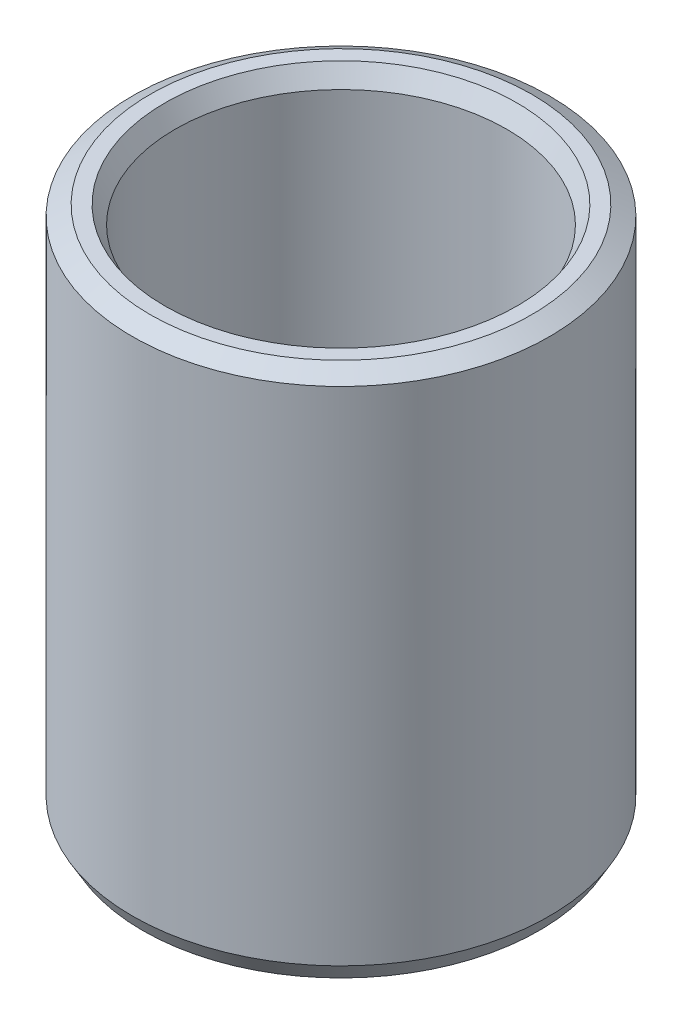
SolidWorks part; units mm, degrees
ref_plane "Front Plane" through (0, 0, 0) normal (0, 0, 1) x (1, 0, 0)
ref_plane "Top Plane" through (0, 0, 0) normal (0, 1, 0) x (1, 0, 0)
ref_plane "Right Plane" through (0, 0, 0) normal (1, 0, 0) x (0, 0, -1)
sketch "Sketch1" plane through (0, 0, 0) normal (0, 1, 0) x (1, 0, 0)
  circle A0 centre (0, 0) radius 45
  dimension "SLEEVE_OD" = 90
extrude "Boss-Extrude1" add sketch "Sketch1" along normal blind 114.3044
sketch "Sketch2" plane through (0, 0, 0) normal (0, 1, 0) x (1, 0, 0)
  circle A0 centre (0, 0) radius 35.7797
  dimension "BORE_D" = 71.5594
extrude "Cut-Extrude1" cut sketch "Sketch2" along normal through all
chamfer "Chamfer1" distance 2.2037 angle 60 4 edges at (0, 114.3044, 35.7797) (0, 0, 35.7797) (0, 0, 45) (0, 114.3044, 45) first distance on face at (0, 114.3044, 35.7797) first distance on face at (0, 0, 35.7797) first distance on face at (0, 114.3044, 45)
